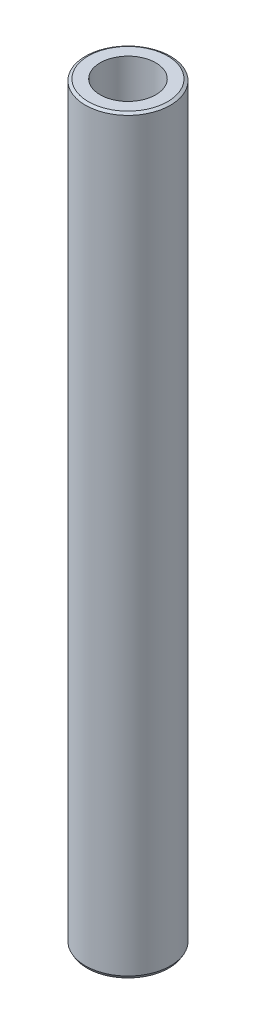
SolidWorks part; units mm, degrees
ref_plane "Front Plane" through (0, 0, 0) normal (0, 0, 1) x (1, 0, 0)
ref_plane "Top Plane" through (0, 0, 0) normal (0, 1, 0) x (1, 0, 0)
ref_plane "Right Plane" through (0, 0, 0) normal (1, 0, 0) x (0, 0, -1)
sketch "Sketch1" plane through (0, 0, 0) normal (0, 1, 0) x (1, 0, 0)
  circle A0 centre (0, 0) radius 15
  dimension "SHAFT_OD" = 30
extrude "Boss-Extrude1" add sketch "Sketch1" along normal blind 264.6634
sketch "Sketch2" plane through (0, 0, 0) normal (0, 1, 0) x (1, 0, 0)
  circle A0 centre (0, 0) radius 9.8103
  dimension "BORE_D" = 19.6206
extrude "Cut-Extrude1" cut sketch "Sketch2" along normal through all
chamfer "Chamfer1" distance 0.5821 angle 60 2 edges at (0, 264.6634, 15) (0, 0, 15) first distance on face at (0, 264.6634, 15) first distance on face at (0, 0, 9.8103)
